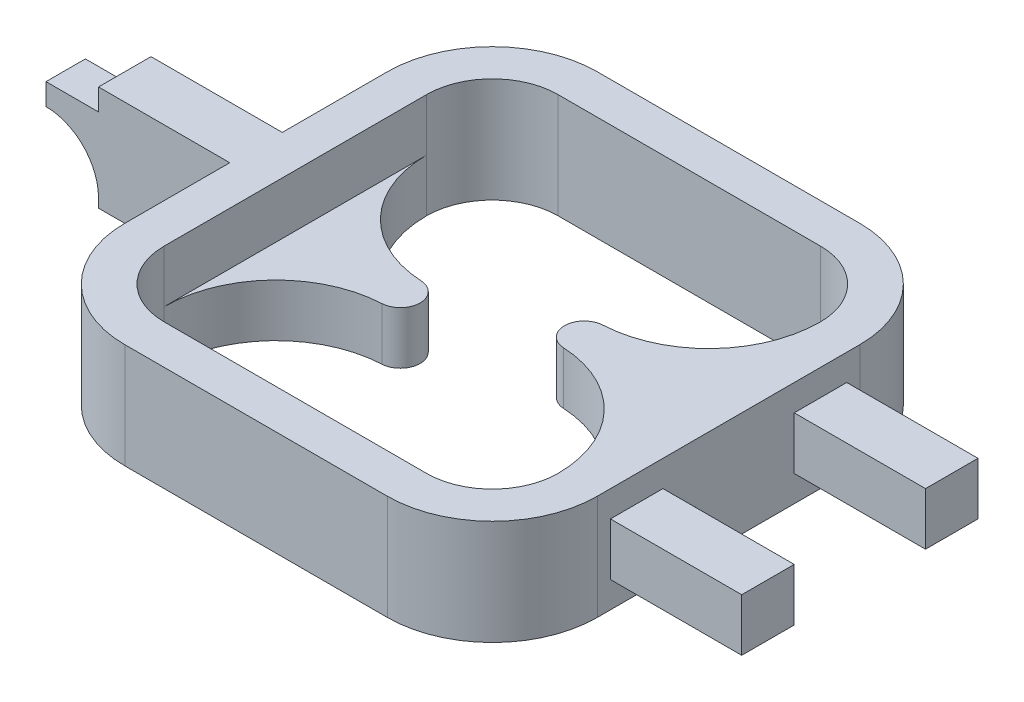
SolidWorks part; units mm, degrees
ref_plane "Front Plane" through (0, 0, 0) normal (0, 0, 1) x (1, 0, 0)
ref_plane "Top Plane" through (0, 0, 0) normal (0, 1, 0) x (1, 0, 0)
ref_plane "Right Plane" through (0, 0, 0) normal (1, 0, 0) x (0, 0, -1)
sketch "Sketch1" plane through (0, 0, 0) normal (0, 1, 0) x (1, 0, 0)
  line L0 (-18, -10) -> (-18, -2)
  line L1 (-10, -15) -> (10, -15)
  line L3 (-10, 15) -> (10, 15)
  line L5 (0, 15) -> (0, -15) construction
  line L6 (-15, 0) -> (15, 0) construction
  line L7 (-10, 18) -> (10, 18)
  line L8 (18, -10) -> (18, -9)
  line L9 (-10, -18) -> (10, -18)
  line L10 (-15, -10) -> (-15, 10) construction
  line L11 (15, -10) -> (15, 10) construction
  line L12 (18, 9) -> (18, 10)
  line L13 (18, 9) -> (28, 9)
  line L15 (18, 5) -> (28, 5)
  line L16 (28, 9) -> (28, 5)
  line L17 (23, 5) -> (23, 9) construction
  line L18 (18, 7) -> (28, 7) construction
  line L19 (18, -10) -> (18, 10) construction
  line L20 (23, -5) -> (23, -9) construction
  line L21 (18, -7) -> (28, -7) construction
  line L22 (18, -5) -> (28, -5)
  line L23 (28, -9) -> (28, -5)
  line L24 (18, -9) -> (28, -9)
  line L25 (18, -5) -> (18, 5)
  line L26 (-18, 2) -> (-18, 10)
  line L27 (-18, 2) -> (-28, 2)
  line L29 (-18, -2) -> (-28, -2)
  line L30 (-28, 2) -> (-28, -2)
  line L31 (-23, -2) -> (-23, 2) construction
  line L32 (-18, 0) -> (-28, 0) construction
  line L33 (-18, -10) -> (-18, 10) construction
  arc A0 (-10, -15) -> (-15, -10) centre (-10, -10) cw
  arc A1 (10, -15) -> (15, -10) centre (10, -10) ccw
  arc A2 (10, 15) -> (15, 10) centre (10, 10) cw
  arc A3 (-15, 10) -> (-10, 15) centre (-10, 10) cw
  arc A4 (-18, 10) -> (-10, 18) centre (-10, 10) cw
  arc A5 (10, 18) -> (18, 10) centre (10, 10) cw
  arc A6 (10, -18) -> (18, -10) centre (10, -10) ccw
  arc A7 (-10, -18) -> (-18, -10) centre (-10, -10) cw
  arc A8 (-6.9231, -1.498) -> (-6.9231, 1.498) centre (-7, 0) ccw
  arc A9 (-15, 10) -> (-6.9231, 1.498) centre (-6.4868, 10) ccw
  arc A10 (-15, -10) -> (-6.9231, -1.498) centre (-6.4868, -10) cw
  arc A11 (15, -10) -> (6.9231, -1.498) centre (6.4868, -10) ccw
  arc A12 (6.9231, -1.498) -> (6.9231, 1.498) centre (7, 0) cw
  arc A13 (15, 10) -> (6.9231, 1.498) centre (6.4868, 10) cw
  point P0 (0, 0)
  point P6 (-15, -15)
  point P14 (-15, 15)
  point P27 (-5.5, 0)
  point P206 (23, 7)
  point P292 (-23, 0)
  dimension "D2" = 5
  dimension "D6" = 3
  dimension "D7" = 8.5132
  dimension "D8" = 8.5132
  dimension "D1" = 30
  dimension "D4" = 36
  dimension "D5" = 20
  dimension "D9" = 30
  dimension "D10" = 3
  dimension "D11" = 9.5
  dimension "D12" = 20
  dimension "D13" = 20
  dimension "D14" = 0.0769
  dimension "D15" = 3
  dimension "D16" = 4
  dimension "D17" = 10
  dimension "D18" = 5
  dimension "D19" = 4
  dimension "D20" = 10
  dimension "D3" = 3
extrude "Boss-Extrude1" add sketch "Sketch1" along normal blind 8
sketch "Sketch2" plane through (-28, 0, 0) normal (-1, 0, 0) x (0, 0, 1)
  line L0 (-2, 8) -> (-2, 0) construction
  line L1 (-1, 6.35) -> (2, 6.35)
  line L2 (-2, 5.35) -> (-2, 4.7)
  line L3 (-2, 4.7) -> (2, 4.7)
  line L4 (2, 6.35) -> (2, 4.7)
  line L5 (0, 4.7) -> (0, 6.35) construction
  line L6 (-2, 5.525) -> (2, 5.525) construction
  line L7 (-2, 4.7) -> (2, 4.7) construction
  line L8 (-2, 8) -> (2, 8) construction
  line L11 (-2, 5.35) -> (-1, 6.35)
  line L12 (2, 8) -> (2, 0) construction
  point P0 (-2, 6.35)
  point P3 (2, 6.35)
  point P64 (0, 5.525)
  dimension "D1" = 1.65
  dimension "D2" = 1.65
extrude "Boss-Extrude2" add sketch "Sketch2" along normal blind 4
sketch "Sketch3" plane through (28, 0, 0) normal (1, 0, 0) x (0, 0, -1)
  line L0 (-9, 4) -> (9, 4) construction
  line L1 (-9, 8) -> (-9, 0) construction
  line L2 (9, 8) -> (9, 0) construction
  line L3 (9, 2) -> (-9, 2) construction
  line L4 (9, 2) -> (9, 6) construction
  line L5 (-9, 2) -> (-9, 6) construction
  line L6 (9, 6) -> (-9, 6) construction
  line L7 (-9, 4) -> (9, 4) construction
  line L8 (0, 2) -> (0, 6) construction
  line L9 (-9, 2) -> (9, 2)
  line L10 (-9, 8) -> (9, 8)
  line L11 (-9, 8) -> (-9, 6)
  line L12 (-9, 6) -> (9, 6)
  line L13 (9, 8) -> (9, 6)
  line L14 (0, 6) -> (0, 8) construction
  line L15 (-9, 7) -> (9, 7) construction
  line L16 (9, 0) -> (9, 2)
  line L17 (-9, 0) -> (9, 0)
  line L18 (-9, 0) -> (-9, 2)
  point P7 (0, 4)
  point P204 (0, 7)
  dimension "D1" = 4
extrude "Cut-Extrude1" cut sketch "Sketch3" against normal up to surface (10 mm away) up to face at (18, 4, 0)
fillet "Fillet1" radius 4 1 edges at (-28, 4.7, 0)
sketch "Sketch4" plane through (0, 0, 0) normal (0, -1, 0) x (1, 0, 0)
  line L1 (15, -10) -> (5.5, -10)
  line L2 (15, -10) -> (15, 10)
  line L3 (15, 10) -> (5.5, 10)
  line L4 (5.5, -10) -> (5.5, 10)
  line L5 (10.25, 10) -> (10.25, -10) construction
  line L6 (15, 0) -> (5.5, 0) construction
  arc A0 (6.9231, 1.498) -> (6.9231, -1.498) centre (7, 0) ccw construction
  point P384 (10.25, 0)
extrude "Cut-Extrude2" cut sketch "Sketch4" against normal blind 4
sketch "Sketch5" plane through (0, 8, 0) normal (0, 1, 0) x (1, 0, 0)
  line L1 (-15, -10) -> (-5.5, -10)
  line L2 (-15, -10) -> (-15, 10)
  line L3 (-15, 10) -> (-5.5, 10)
  line L4 (-5.5, -10) -> (-5.5, 10)
  line L5 (-10.25, 10) -> (-10.25, -10) construction
  line L6 (-15, 0) -> (-5.5, 0) construction
  arc A0 (-6.9231, -1.498) -> (-6.9231, 1.498) centre (-7, 0) ccw construction
  point P348 (-10.25, 0)
extrude "Cut-Extrude3" cut sketch "Sketch5" against normal blind 4
equation "\"D8@Sketch1\"=\"D7@Sketch1\""
